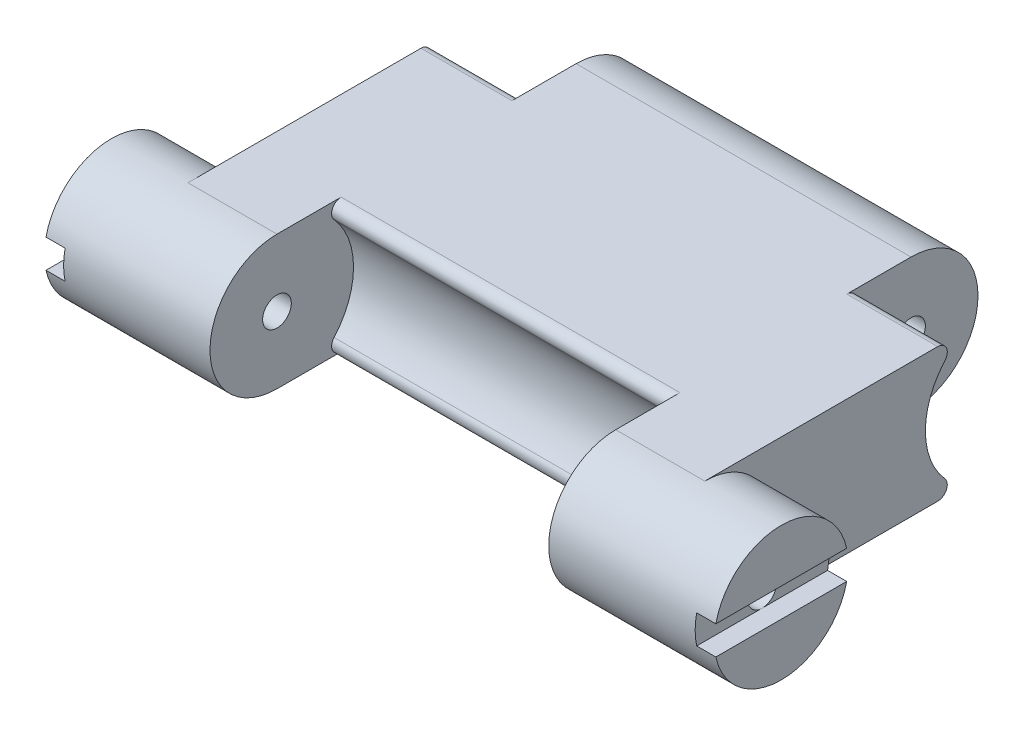
SolidWorks part; units mm, degrees
ref_plane "Спереди" through (0, 0, 0) normal (0, 0, 1) x (1, 0, 0)
ref_plane "Сверху" through (0, 0, 0) normal (0, 1, 0) x (1, 0, 0)
ref_plane "Справа" through (0, 0, 0) normal (1, 0, 0) x (0, 0, -1)
sketch "Эскиз1" plane through (0, 0, 0) normal (1, 0, 0) x (0, 0, -1)
  line L0 (-7.765, 3.5) -> (7.765, 3.5) construction
  line L1 (-7.765, 7) -> (7.765, 7)
  line L2 (-7.765, 0) -> (7.765, 0)
  arc A0 (-7.765, 7) -> (-7.765, 0) centre (-7.765, 3.5) ccw
  arc A1 (7.765, 0) -> (7.765, 7) centre (7.765, 3.5) ccw
  point P2 (0, 3.5)
  dimension "D1" = 15.53
  dimension "D2" = 7
extrude "Бобышка-Вытянуть1" add sketch "Эскиз1" along normal mid plane 35
sketch "Эскиз3" plane through (17.5, 0, 0) normal (1, 0, 0) x (0, 0, -1)
  line L0 (7.765, 7) -> (-7.765, 7) construction
  line L1 (-12, 8) -> (12, 8)
  line L2 (-12, 8) -> (-12, -1)
  line L3 (-12, -1) -> (12, -1)
  line L4 (12, 8) -> (12, -1)
  line L5 (-12, 8) -> (12, -1) construction
  line L6 (-12, -1) -> (12, 8) construction
  line L7 (-7.765, 0) -> (7.765, 0) construction
  circle A0 centre (-7.765, 3.5) radius 3.5
  arc A1 (-7.765, 7) -> (-7.765, 0) centre (-7.765, 3.5) ccw construction
  point P9 (0, 3.5)
  dimension "D1" = 1
  dimension "D2" = 1
  dimension "D3" = 12
  dimension "D4" = 24
extrude "Вырез-Вытянуть1" cut sketch "Эскиз3" against normal blind 4
mirror "Зеркальное отражение1" about plane through (0, 0, 0) normal (1, 0, 0) of "Вырез-Вытянуть1"
sketch "Эскиз6" plane through (0, 0, 0) normal (1, 0, 0) x (0, 0, -1)
  circle A0 centre (-7.765, 3.5) radius 4
  circle A1 centre (-7.765, 3.5) radius 3.5 construction
  dimension "D1" = 8
extrude "Вырез-Вытянуть2" cut sketch "Эскиз6" against normal mid plane 17.7
sketch "Эскиз7" plane through (13.5, 0, 0) normal (1, 0, 0) x (0, 0, -1)
  circle A0 centre (7.765, 3.5) radius 4
  arc A1 (7.765, 0) -> (7.765, 7) centre (7.765, 3.5) ccw construction
  dimension "D2" = 8
  dimension "D1" = 0
extrude "Вырез-Вытянуть3" cut sketch "Эскиз7" against normal blind 4.75
sketch "Эскиз9" plane through (17.5, 0, 0) normal (1, 0, 0) x (0, 0, -1)
  line L1 (-11.365, 2.75) -> (-4.165, 2.75)
  line L2 (-11.365, 2.75) -> (-11.365, 4.25)
  line L3 (-11.365, 4.25) -> (-4.165, 4.25)
  line L4 (-4.165, 2.75) -> (-4.165, 4.25)
  line L5 (-11.365, 2.75) -> (-4.165, 4.25) construction
  line L6 (-11.365, 4.25) -> (-4.165, 2.75) construction
  circle A0 centre (-7.765, 3.5) radius 3.5 construction
  circle A1 centre (-7.765, 3.5) radius 3.5 construction
  point P4 (-7.765, 3.5)
  dimension "D1" = 1.5
  dimension "D2" = 7.2
extrude "Вырез-Вытянуть5" cut sketch "Эскиз9" against normal blind 1
mirror "Зеркальное отражение2" about plane through (0, 0, 0) normal (1, 0, 0) of "Вырез-Вытянуть5", "Вырез-Вытянуть3"
fillet "Скругление1" radius 0.5 6 edges at (-11.125, 0, -5.8285) (-11.125, 7, -5.8285) (0, 7, 5.8285) (0, 0, 5.8285) (11.125, 7, -5.8285) (11.125, 0, -5.8285)
sketch "Эскиз8" plane through (17.5, 0, 0) normal (1, 0, 0) x (0, 0, -1)
  circle A0 centre (-7.765, 3.5) radius 0.75
  circle A1 centre (7.765, 3.5) radius 0.75
  arc A2 (7.765, 0) -> (7.765, 7) centre (7.765, 3.5) ccw construction
  circle A3 centre (-7.765, 3.5) radius 3.5 construction
  dimension "D1" = 1.5
extrude "Вырез-Вытянуть4" cut sketch "Эскиз8" against normal through all
ref_plane "Плоскость4" through (-15.5, 0, 0) normal (-1, 0, 0) x (0, 0, 1)
